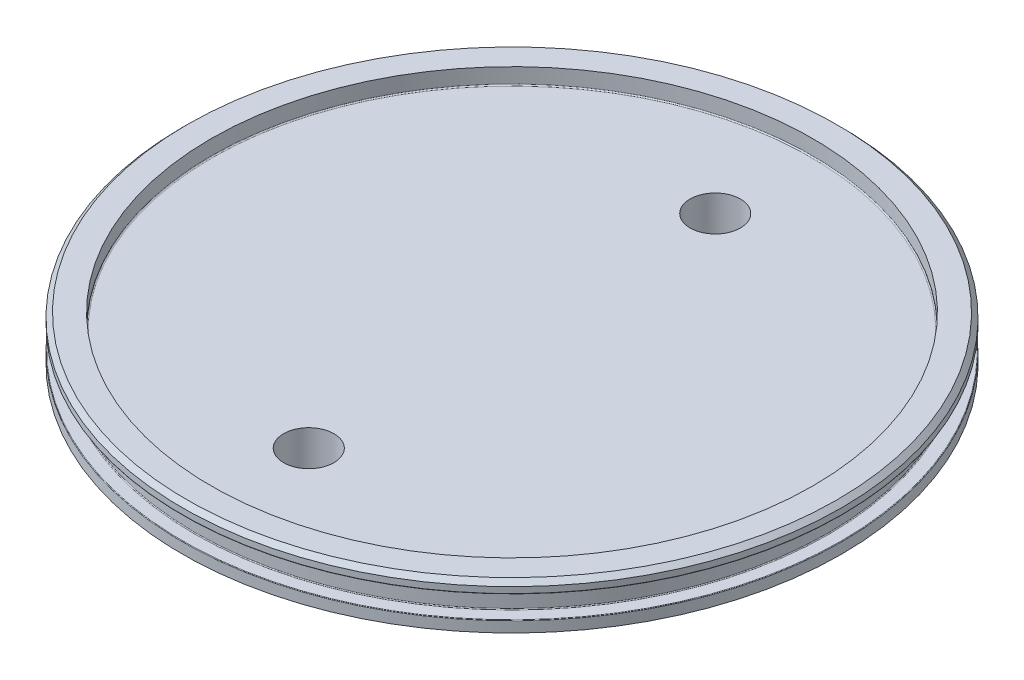
SolidWorks part; units mm, degrees
material "6061-T6 (SS)"
ref_plane "Front Plane" through (0, 0, 0) normal (0, 0, 1) x (1, 0, 0)
ref_plane "Top Plane" through (0, 0, 0) normal (0, 1, 0) x (1, 0, 0)
ref_plane "Right Plane" through (0, 0, 0) normal (1, 0, 0) x (0, 0, -1)
sketch "Sketch1" plane through (0, 0, 0) normal (0, 0, 1) x (1, 0, 0)
  line L0 (0, 48.1922) -> (0, -25.6743) construction
  line L1 (0, 0) -> (72.898, 0)
  line L2 (72.898, 0) -> (72.898, 2.4638)
  line L3 (72.898, 2.4638) -> (69.977, 2.4638)
  line L4 (69.977, 2.4638) -> (69.977, 7.4422)
  line L5 (69.977, 7.4422) -> (72.898, 7.4422)
  line L6 (72.898, 7.4422) -> (72.898, 9.906)
  line L7 (72.898, 9.906) -> (66.548, 9.906)
  line L8 (66.548, 9.906) -> (66.548, 6.35)
  line L9 (66.548, 6.35) -> (0, 6.35)
  line L10 (0, 6.35) -> (0, 0)
  dimension "D1" = 145.796
  dimension "D2" = 4.9784
  dimension "D3" = 2.921
  dimension "D4" = 9.906
  dimension "D5" = 6.35
  dimension "D6" = 6.35
revolve "Revolve1" add sketch "Sketch1" angle 360 about L0
sketch "Sketch6" plane through (0, 0, 0) normal (0, -1, 0) x (1, 0, 0)
  circle A0 centre (0, 0) radius 66.04
  dimension "D1" = 132.08
extrude "Boss-Extrude1" add sketch "Sketch6" along normal blind 2.54
fillet "CNC ID Fillet" radius 0.1778 3 edges at (-69.977, 7.4422, 0) (-69.977, 2.4638, 0) (66.04, 0, 0)
fillet "CNC OD Fillet" radius 0.127 3 edges at (-72.898, 7.4422, 0) (-72.898, 2.4638, 0) (66.04, -2.54, 0)
chamfer "CNC Chamfers" distance 1.016 angle 45 1 edges at (-72.898, 9.906, 0)
fillet "CNC Bore Fillet" radius 0.254 1 edges at (-66.548, 6.35, 0)
hole_wizard "Pipe Tap Drill for 1/4 Tap - Relief Valve" positions "Sketch13" profile "Sketch14" hole size "1/4" standard "ANSI Inch" end condition through all
sketch "Sketch13" plane through (0, -2.54, 0) normal (0, -1, 0) x (-1, 0, 0)
  point P4 (0, 44.958)
  dimension "D1" = 44.958
sketch "Sketch14" plane through (0, -2.54, -44.958) normal (1, 0, 0) x (0, 0, -1)
  line L0 (0, 0) -> (0, 12.446)
  line L1 (0, 12.446) -> (5.5626, 12.446)
  line L2 (5.5626, 12.446) -> (5.5626, 0)
  line L5 (5.5626, 0) -> (0, 0)
  line L11 (0, -6.35) -> (0, 107.95) construction
  dimension "Thru Hole Dia." = 11.1252
  dimension "Thru Hole Depth" = 12.446
hole_wizard "Pipe Tap Drill for 1/4 Tap - Vent Valve" positions "Sketch15" profile "Sketch16" hole size "1/4" standard "ANSI Inch" end condition through all
sketch "Sketch15" plane through (0, -2.54, 0) normal (0, -1, 0) x (-1, 0, 0)
  point P4 (0, -44.958)
  dimension "D1" = 44.958
sketch "Sketch16" plane through (0, -2.54, 44.958) normal (1, 0, 0) x (0, 0, -1)
  line L0 (0, 0) -> (0, 12.446)
  line L1 (0, 12.446) -> (5.5626, 12.446)
  line L2 (5.5626, 12.446) -> (5.5626, 0)
  line L5 (5.5626, 0) -> (0, 0)
  line L11 (0, -6.35) -> (0, 107.95) construction
  dimension "Thru Hole Dia." = 11.1252
  dimension "Thru Hole Depth" = 12.446
